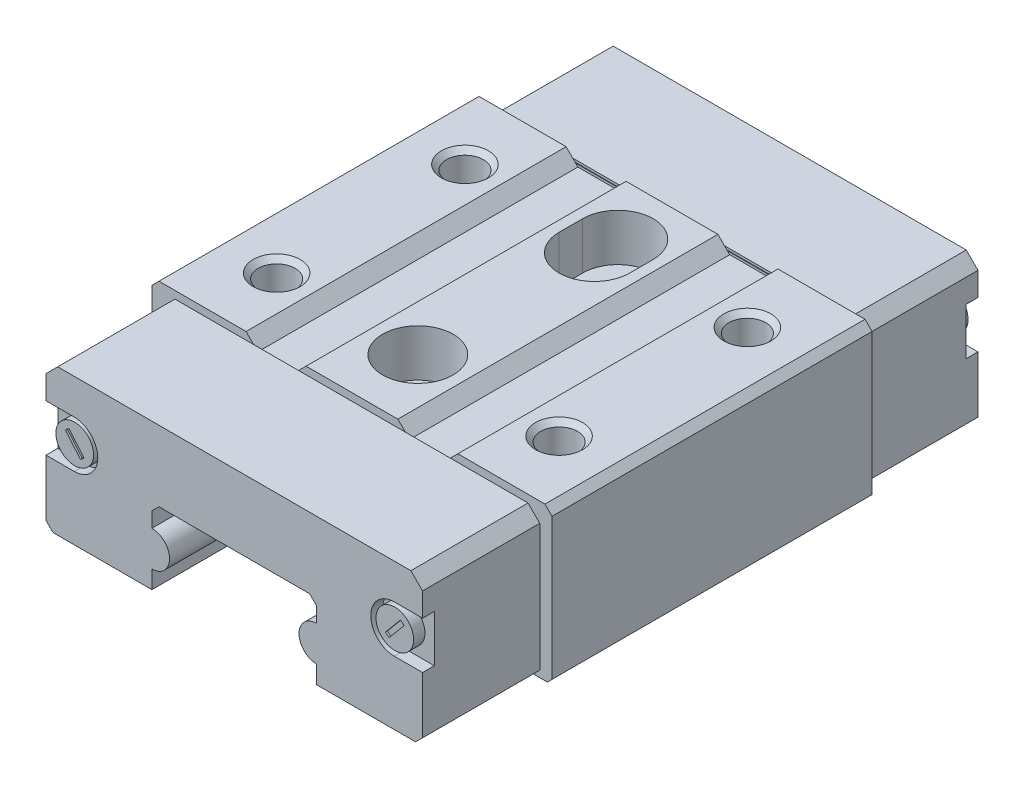
SolidWorks part; units mm, degrees
material "Plain Carbon Steel"
ref_plane "Front Plane" through (0, 0, 0) normal (0, 0, 1) x (1, 0, 0)
ref_plane "Top Plane" through (0, 0, 0) normal (0, 1, 0) x (1, 0, 0)
ref_plane "Right Plane" through (0, 0, 0) normal (1, 0, 0) x (0, 0, -1)
ref_plane "Plane1" through (0, 0, 0) normal (0, 0, 1) x (1, 0, 0)
sketch "Sketch1" plane through (0, 0, 0) normal (0, 0, 1) x (1, 0, 0)
  line L0 (-8.5, 6.2) -> (-8.5, 0.198)
  line L1 (-8.5, 0.198) -> (-8.302, 0)
  line L2 (-8.302, 0) -> (-3.5, 0)
  line L3 (-3.5, 0) -> (-3.5, 0.76)
  line L4 (-3.5, 2.26) -> (-3.5, 2.903)
  line L5 (-3.5, 2.903) -> (-3.203, 3.2)
  line L6 (-3.203, 3.2) -> (3.203, 3.2)
  line L7 (3.203, 3.2) -> (3.5, 2.903)
  line L8 (3.5, 2.903) -> (3.5, 2.26)
  line L9 (3.5, 0.76) -> (3.5, 0)
  line L10 (3.5, 0) -> (8.302, 0)
  line L11 (8.302, 0) -> (8.5, 0.198)
  line L12 (8.5, 0.198) -> (8.5, 6.2)
  line L13 (8.5, 6.2) -> (8.2, 6.5)
  line L14 (8.2, 6.5) -> (4.5, 6.5)
  line L15 (4.5, 6.5) -> (4, 6)
  line L16 (4, 6) -> (2.45, 6)
  line L17 (2.45, 6) -> (1.95, 6.5)
  line L18 (1.95, 6.5) -> (-1.95, 6.5)
  line L19 (-1.95, 6.5) -> (-2.45, 6)
  line L20 (-2.45, 6) -> (-4, 6)
  line L21 (-4, 6) -> (-4.5, 6.5)
  line L22 (-4.5, 6.5) -> (-8.2, 6.5)
  line L23 (-8.2, 6.5) -> (-8.5, 6.2)
  arc A0 (-3.5, 0.76) -> (-3.5, 2.26) centre (-3.5, 1.51) ccw
  arc A1 (3.5, 2.26) -> (3.5, 0.76) centre (3.5, 1.51) ccw
extrude "Boss-Extrude1" add sketch "Sketch1" against normal blind 6.8 and the other way blind 6.8
ref_plane "Plane2" through (0, 0, 6.8) normal (0, 0, 1) x (1, 0, 0)
sketch "Sketch2" plane through (0, 0, 6.8) normal (0, 0, 1) x (1, 0, 0)
  line L0 (-8, 5.7015) -> (-8, 0.297)
  line L1 (-8, 0.297) -> (-7.703, 0)
  line L2 (-7.703, 0) -> (-3.5, 0)
  line L3 (-3.5, 0) -> (-3.5, 0.76)
  line L4 (-3.5, 2.26) -> (-3.5, 2.903)
  line L5 (-3.5, 2.903) -> (-3.203, 3.2)
  line L6 (-3.203, 3.2) -> (3.203, 3.2)
  line L7 (3.203, 3.2) -> (3.5, 2.903)
  line L8 (3.5, 2.903) -> (3.5, 2.26)
  line L9 (3.5, 0.76) -> (3.5, 0)
  line L10 (3.5, 0) -> (7.703, 0)
  line L11 (7.703, 0) -> (8, 0.297)
  line L12 (8, 0.297) -> (8, 5.7015)
  line L13 (8, 5.7015) -> (7.5015, 6.2)
  line L14 (7.5015, 6.2) -> (-7.5015, 6.2)
  line L15 (-7.5015, 6.2) -> (-8, 5.7015)
  arc A0 (-3.5, 0.76) -> (-3.5, 2.26) centre (-3.5, 1.51) ccw
  arc A1 (3.5, 2.26) -> (3.5, 0.76) centre (3.5, 1.51) ccw
extrude "Boss-Extrude2" add sketch "Sketch2" along normal blind 5
ref_plane "Plane3" through (0, 0, 6.8) normal (0, 0, 1) x (1, 0, 0)
sketch "Sketch3" plane through (0, 0, 6.8) normal (0, 0, 1) x (1, 0, 0)
  line L0 (-40, 40) -> (-40, -40)
  line L1 (-40, -40) -> (40, -40)
  line L2 (40, -40) -> (40, 40)
  line L3 (40, 40) -> (-40, 40)
  line L4 (-7.9, 5.6015) -> (-7.9, 0.397)
  line L5 (-7.9, 0.397) -> (-7.603, 0.1)
  line L6 (-7.603, 0.1) -> (-3.6, 0.1)
  line L7 (-3.6, 0.1) -> (-3.6, 0.86)
  line L8 (-3.6, 2.16) -> (-3.6, 3.003)
  line L9 (-3.6, 3.003) -> (-3.303, 3.3)
  line L10 (-3.303, 3.3) -> (3.303, 3.3)
  line L11 (3.303, 3.3) -> (3.6, 3.003)
  line L12 (3.6, 3.003) -> (3.6, 2.16)
  line L13 (3.6, 0.86) -> (3.6, 0.1)
  line L14 (3.6, 0.1) -> (7.603, 0.1)
  line L15 (7.603, 0.1) -> (7.9, 0.397)
  line L16 (7.9, 0.397) -> (7.9, 5.6015)
  line L17 (7.9, 5.6015) -> (7.4015, 6.1)
  line L18 (7.4015, 6.1) -> (-7.4015, 6.1)
  line L19 (-7.4015, 6.1) -> (-7.9, 5.6015)
  arc A0 (-3.6, 0.86) -> (-3.6, 2.16) centre (-3.6, 1.51) ccw
  arc A1 (3.6, 2.16) -> (3.6, 0.86) centre (3.6, 1.51) ccw
extrude "Cut-Extrude1" cut sketch "Sketch3" along normal blind 0.02
ref_plane "Plane4" through (0, 0, -6.8) normal (0, 0, 1) x (1, 0, 0)
sketch "Sketch4" plane through (0, 0, -6.8) normal (0, 0, 1) x (1, 0, 0)
  line L0 (-8, 5.7015) -> (-8, 0.297)
  line L1 (-8, 0.297) -> (-7.703, 0)
  line L2 (-7.703, 0) -> (-3.5, 0)
  line L3 (-3.5, 0) -> (-3.5, 0.76)
  line L4 (-3.5, 2.26) -> (-3.5, 2.903)
  line L5 (-3.5, 2.903) -> (-3.203, 3.2)
  line L6 (-3.203, 3.2) -> (3.203, 3.2)
  line L7 (3.203, 3.2) -> (3.5, 2.903)
  line L8 (3.5, 2.903) -> (3.5, 2.26)
  line L9 (3.5, 0.76) -> (3.5, 0)
  line L10 (3.5, 0) -> (7.703, 0)
  line L11 (7.703, 0) -> (8, 0.297)
  line L12 (8, 0.297) -> (8, 5.7015)
  line L13 (8, 5.7015) -> (7.5015, 6.2)
  line L14 (7.5015, 6.2) -> (-7.5015, 6.2)
  line L15 (-7.5015, 6.2) -> (-8, 5.7015)
  arc A0 (-3.5, 0.76) -> (-3.5, 2.26) centre (-3.5, 1.51) ccw
  arc A1 (3.5, 2.26) -> (3.5, 0.76) centre (3.5, 1.51) ccw
extrude "Boss-Extrude3" add sketch "Sketch4" against normal blind 5
ref_plane "Plane5" through (0, 0, -6.8) normal (0, 0, 1) x (1, 0, 0)
sketch "Sketch5" plane through (0, 0, -6.8) normal (0, 0, 1) x (1, 0, 0)
  line L0 (-40, 40) -> (-40, -40)
  line L1 (-40, -40) -> (40, -40)
  line L2 (40, -40) -> (40, 40)
  line L3 (40, 40) -> (-40, 40)
  line L4 (-7.9, 5.6015) -> (-7.9, 0.397)
  line L5 (-7.9, 0.397) -> (-7.603, 0.1)
  line L6 (-7.603, 0.1) -> (-3.6, 0.1)
  line L7 (-3.6, 0.1) -> (-3.6, 0.86)
  line L8 (-3.6, 2.16) -> (-3.6, 3.003)
  line L9 (-3.6, 3.003) -> (-3.303, 3.3)
  line L10 (-3.303, 3.3) -> (3.303, 3.3)
  line L11 (3.303, 3.3) -> (3.6, 3.003)
  line L12 (3.6, 3.003) -> (3.6, 2.16)
  line L13 (3.6, 0.86) -> (3.6, 0.1)
  line L14 (3.6, 0.1) -> (7.603, 0.1)
  line L15 (7.603, 0.1) -> (7.9, 0.397)
  line L16 (7.9, 0.397) -> (7.9, 5.6015)
  line L17 (7.9, 5.6015) -> (7.4015, 6.1)
  line L18 (7.4015, 6.1) -> (-7.4015, 6.1)
  line L19 (-7.4015, 6.1) -> (-7.9, 5.6015)
  arc A0 (-3.6, 0.86) -> (-3.6, 2.16) centre (-3.6, 1.51) ccw
  arc A1 (3.6, 2.16) -> (3.6, 0.86) centre (3.6, 1.51) ccw
extrude "Cut-Extrude2" cut sketch "Sketch5" against normal blind 0.02
ref_plane "Plane6" through (0, 0, -11.8) normal (0, 0, 1) x (1, 0, 0)
sketch "Sketch6" plane through (0, 0, -11.8) normal (0, 0, 1) x (1, 0, 0)
  line L0 (-13.6, 2.7) -> (-6.8, 2.7)
  line L1 (-6.8, 4.7) -> (-12.6, 4.7)
  line L2 (-12.6, 4.7) -> (-12.6, 7.7)
  line L3 (-12.6, 7.7) -> (12.6, 7.7)
  line L4 (12.6, 7.7) -> (12.6, 4.7)
  line L5 (12.6, 4.7) -> (6.8, 4.7)
  line L6 (6.8, 2.7) -> (13.6, 2.7)
  line L7 (13.6, 2.7) -> (13.6, 9.7)
  line L8 (13.6, 9.7) -> (-13.6, 9.7)
  line L9 (-13.6, 9.7) -> (-13.6, 2.7)
  arc A0 (-6.8, 2.7) -> (-6.8, 4.7) centre (-6.8, 3.7) ccw
  arc A1 (6.8, 4.7) -> (6.8, 2.7) centre (6.8, 3.7) ccw
extrude "Cut-Extrude3" cut sketch "Sketch6" along normal blind 0.02
ref_plane "Plane7" through (0, 0, 11.8) normal (0, 0, 1) x (1, 0, 0)
sketch "Sketch7" plane through (0, 0, 11.8) normal (0, 0, 1) x (1, 0, 0)
  line L0 (-13.6, 2.7) -> (-6.8, 2.7)
  line L1 (-6.8, 4.7) -> (-12.6, 4.7)
  line L2 (-12.6, 4.7) -> (-12.6, 7.7)
  line L3 (-12.6, 7.7) -> (12.6, 7.7)
  line L4 (12.6, 7.7) -> (12.6, 4.7)
  line L5 (12.6, 4.7) -> (6.8, 4.7)
  line L6 (6.8, 2.7) -> (13.6, 2.7)
  line L7 (13.6, 2.7) -> (13.6, 9.7)
  line L8 (13.6, 9.7) -> (-13.6, 9.7)
  line L9 (-13.6, 9.7) -> (-13.6, 2.7)
  arc A0 (-6.8, 2.7) -> (-6.8, 4.7) centre (-6.8, 3.7) ccw
  arc A1 (6.8, 4.7) -> (6.8, 2.7) centre (6.8, 3.7) ccw
  circle A2 centre (6.8, 3.7) radius 0.8
  circle A3 centre (-6.8, 3.7) radius 0.8
extrude "Cut-Extrude4" cut sketch "Sketch7" against normal blind 0.5
ref_plane "Plane8" through (0, 0, 11.8) normal (0, 0, 1) x (1, 0, 0)
sketch "Sketch8" plane through (0, 0, 11.8) normal (0, 0, 1) x (1, 0, 0)
  line L0 (-13.6, 2.7) -> (-6.8, 2.7)
  line L1 (-6.8, 4.7) -> (-12.6, 4.7)
  line L2 (-12.6, 4.7) -> (-12.6, 7.7)
  line L3 (-12.6, 7.7) -> (12.6, 7.7)
  line L4 (12.6, 7.7) -> (12.6, 4.7)
  line L5 (12.6, 4.7) -> (6.8, 4.7)
  line L6 (6.8, 2.7) -> (13.6, 2.7)
  line L7 (13.6, 2.7) -> (13.6, 9.7)
  line L8 (13.6, 9.7) -> (-13.6, 9.7)
  line L9 (-13.6, 9.7) -> (-13.6, 2.7)
  arc A0 (-6.8, 2.7) -> (-6.8, 4.7) centre (-6.8, 3.7) ccw
  arc A1 (6.8, 4.7) -> (6.8, 2.7) centre (6.8, 3.7) ccw
extrude "Cut-Extrude5" cut sketch "Sketch8" against normal blind 0.02
ref_plane "Plane9" through (0, 0, -11.8) normal (0, 0, 1) x (1, 0, 0)
sketch "Sketch9" plane through (0, 0, -11.8) normal (0, 0, 1) x (1, 0, 0)
  line L0 (-13.6, 2.7) -> (-6.8, 2.7)
  line L1 (-6.8, 4.7) -> (-12.6, 4.7)
  line L2 (-12.6, 4.7) -> (-12.6, 7.7)
  line L3 (-12.6, 7.7) -> (12.6, 7.7)
  line L4 (12.6, 7.7) -> (12.6, 4.7)
  line L5 (12.6, 4.7) -> (6.8, 4.7)
  line L6 (6.8, 2.7) -> (13.6, 2.7)
  line L7 (13.6, 2.7) -> (13.6, 9.7)
  line L8 (13.6, 9.7) -> (-13.6, 9.7)
  line L9 (-13.6, 9.7) -> (-13.6, 2.7)
  arc A0 (-6.8, 2.7) -> (-6.8, 4.7) centre (-6.8, 3.7) ccw
  arc A1 (6.8, 4.7) -> (6.8, 2.7) centre (6.8, 3.7) ccw
  circle A2 centre (6.8, 3.7) radius 0.8
  circle A3 centre (-6.8, 3.7) radius 0.8
extrude "Cut-Extrude6" cut sketch "Sketch9" along normal blind 0.5
ref_plane "Plane10" through (6, 0, 0) normal (1, 0, 0) x (0, 0, -1)
sketch "Sketch10" plane through (6, 0, 0) normal (1, 0, 0) x (0, 0, -1)
  line L0 (-4, 6.5) -> (-3, 6.5)
  line L1 (-3, 6.5) -> (-3.2165, 6.2835)
  line L2 (-3.2165, 6.2835) -> (-3.2165, 3.25)
  line L3 (-3.2165, 3.25) -> (-4, 2.7976)
  line L4 (-4, 2.7976) -> (-4, 6.5)
  line L5 (-4, 2.7976) -> (-4, 6.5) construction
revolve "Cut-Revolve1" cut sketch "Sketch10" angle 360 about L5 reverse direction yes
ref_plane "Plane11" through (-6, 0, 0) normal (1, 0, 0) x (0, 0, -1)
sketch "Sketch11" plane through (-6, 0, 0) normal (1, 0, 0) x (0, 0, -1)
  line L0 (4, 6.5) -> (5, 6.5)
  line L1 (5, 6.5) -> (4.7835, 6.2835)
  line L2 (4.7835, 6.2835) -> (4.7835, 3.25)
  line L3 (4.7835, 3.25) -> (4, 2.7976)
  line L4 (4, 2.7976) -> (4, 6.5)
  line L5 (4, 2.7976) -> (4, 6.5) construction
revolve "Cut-Revolve2" cut sketch "Sketch11" angle 360 about L5 reverse direction yes
ref_plane "Plane12" through (6, 0, 0) normal (1, 0, 0) x (0, 0, -1)
sketch "Sketch12" plane through (6, 0, 0) normal (1, 0, 0) x (0, 0, -1)
  line L0 (4, 6.5) -> (5, 6.5)
  line L1 (5, 6.5) -> (4.7835, 6.2835)
  line L2 (4.7835, 6.2835) -> (4.7835, 3.25)
  line L3 (4.7835, 3.25) -> (4, 2.7976)
  line L4 (4, 2.7976) -> (4, 6.5)
  line L5 (4, 2.7976) -> (4, 6.5) construction
revolve "Cut-Revolve3" cut sketch "Sketch12" angle 360 about L5 reverse direction yes
ref_plane "Plane13" through (-6, 0, 0) normal (1, 0, 0) x (0, 0, -1)
sketch "Sketch13" plane through (-6, 0, 0) normal (1, 0, 0) x (0, 0, -1)
  line L0 (-4, 6.5) -> (-3, 6.5)
  line L1 (-3, 6.5) -> (-3.2165, 6.2835)
  line L2 (-3.2165, 6.2835) -> (-3.2165, 3.25)
  line L3 (-3.2165, 3.25) -> (-4, 2.7976)
  line L4 (-4, 2.7976) -> (-4, 6.5)
  line L5 (-4, 2.7976) -> (-4, 6.5) construction
revolve "Cut-Revolve4" cut sketch "Sketch13" angle 360 about L5 reverse direction yes
ref_plane "Plane14" through (0, 0, 0) normal (1, 0, 0) x (0, 0, -1)
sketch "Sketch14" plane through (0, 0, 0) normal (1, 0, 0) x (0, 0, -1)
  line L0 (-4, 4.5) -> (-5.5, 4.5)
  line L1 (-5.5, 4.5) -> (-5.5, 6.5)
  line L2 (-5.5, 6.5) -> (-4, 6.5)
  line L3 (-4, 6.5) -> (-4, 4.5)
  line L4 (-4, 6.5) -> (-4, 4.5) construction
revolve "Cut-Revolve5" cut sketch "Sketch14" angle 360 about L4 reverse direction yes
ref_plane "Plane15" through (0, 6.5, 0) normal (0, 1, 0) x (-1, 0, 0)
sketch "Sketch15" plane through (0, 6.5, 0) normal (0, 1, 0) x (-1, 0, 0)
  line L0 (1.5, -4.5) -> (1.5, -3.5)
  line L1 (-1.5, -3.5) -> (-1.5, -4.5)
  arc A0 (1.5, -3.5) -> (0, -2) centre (0, -3.5) ccw
  arc A1 (0, -2) -> (-1.5, -3.5) centre (0, -3.5) ccw
  arc A2 (-1.5, -4.5) -> (0, -6) centre (0, -4.5) ccw
  arc A3 (0, -6) -> (1.5, -4.5) centre (0, -4.5) ccw
extrude "Cut-Extrude7" cut sketch "Sketch15" against normal blind 2
ref_plane "Plane16" through (0, 0, 11.8) normal (0, 0, 1) x (1, 0, 0)
sketch "Sketch16" plane through (0, 0, 11.8) normal (0, 0, 1) x (1, 0, 0)
  line L0 (6.402, 3.3813) -> (6.5552, 3.2527)
  line L1 (6.5552, 3.2527) -> (7.198, 4.0187)
  line L2 (7.198, 4.0187) -> (7.0448, 4.1473)
  line L3 (7.0448, 4.1473) -> (6.402, 3.3813)
extrude "Cut-Extrude8" cut sketch "Sketch16" against normal blind 0.1
ref_plane "Plane17" through (0, 0, 11.8) normal (0, 0, 1) x (1, 0, 0)
sketch "Sketch17" plane through (0, 0, 11.8) normal (0, 0, 1) x (1, 0, 0)
  line L0 (-7.198, 4.0187) -> (-6.5552, 3.2527)
  line L1 (-6.5552, 3.2527) -> (-6.402, 3.3813)
  line L2 (-6.402, 3.3813) -> (-7.0448, 4.1473)
  line L3 (-7.0448, 4.1473) -> (-7.198, 4.0187)
extrude "Cut-Extrude9" cut sketch "Sketch17" against normal blind 0.1
ref_plane "Plane18" through (0, 0, -11.8) normal (0, 0, 1) x (1, 0, 0)
sketch "Sketch18" plane through (0, 0, -11.8) normal (0, 0, 1) x (1, 0, 0)
  line L0 (6.402, 3.3813) -> (6.5552, 3.2527)
  line L1 (6.5552, 3.2527) -> (7.198, 4.0187)
  line L2 (7.198, 4.0187) -> (7.0448, 4.1473)
  line L3 (7.0448, 4.1473) -> (6.402, 3.3813)
extrude "Cut-Extrude10" cut sketch "Sketch18" along normal blind 0.1
ref_plane "Plane19" through (0, 0, -11.8) normal (0, 0, 1) x (1, 0, 0)
sketch "Sketch19" plane through (0, 0, -11.8) normal (0, 0, 1) x (1, 0, 0)
  line L0 (-7.198, 4.0187) -> (-6.5552, 3.2527)
  line L1 (-6.5552, 3.2527) -> (-6.402, 3.3813)
  line L2 (-6.402, 3.3813) -> (-7.0448, 4.1473)
  line L3 (-7.0448, 4.1473) -> (-7.198, 4.0187)
extrude "Cut-Extrude11" cut sketch "Sketch19" along normal blind 0.1
